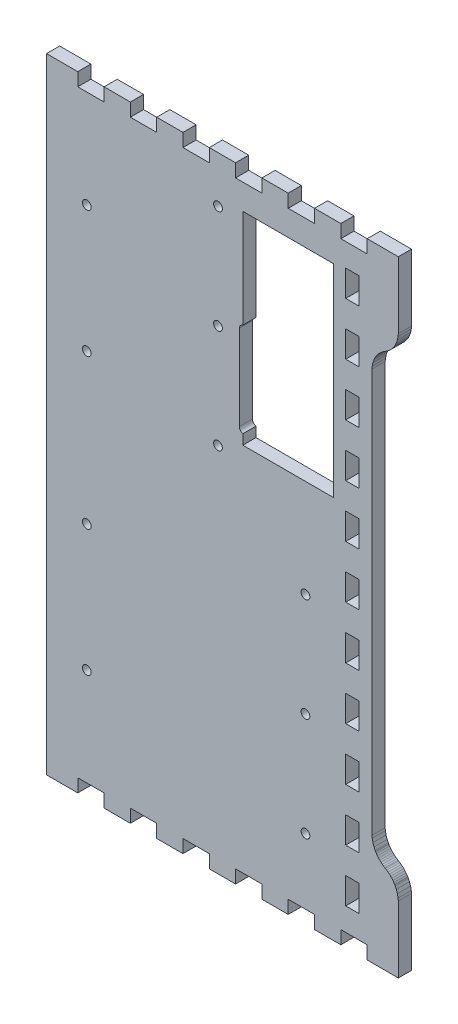
SolidWorks part; units mm, degrees
ref_plane "Front Plane" through (0, 0, 0) normal (0, 0, 1) x (1, 0, 0)
ref_plane "Top Plane" through (0, 0, 0) normal (0, 1, 0) x (1, 0, 0)
ref_plane "Right Plane" through (0, 0, 0) normal (1, 0, 0) x (0, 0, -1)
sketch "Model" plane through (0, 0, 0) normal (0, 0, 1) x (1, 0, 0)
  line L947 (1382.75, 22.8575) -> (1396.32, 22.8575)
  line L948 (1396.32, 22.8575) -> (1396.32, 28.5722)
  line L949 (1396.32, 28.5722) -> (1407.75, 28.5722)
  line L950 (1407.75, 28.5722) -> (1407.75, 22.8575)
  line L951 (1407.75, 22.8575) -> (1419.18, 22.8575)
  line L952 (1419.18, 22.8575) -> (1419.18, 28.5722)
  line L953 (1419.18, 28.5722) -> (1430.61, 28.5722)
  line L954 (1430.61, 28.5722) -> (1430.61, 22.8575)
  line L955 (1430.61, 22.8575) -> (1442.04, 22.8575)
  line L956 (1442.04, 22.8575) -> (1442.04, 28.5722)
  line L957 (1442.04, 28.5722) -> (1453.47, 28.5722)
  line L958 (1453.47, 28.5722) -> (1453.47, 22.8575)
  line L959 (1453.47, 22.8575) -> (1464.9, 22.8575)
  line L960 (1464.9, 22.8575) -> (1464.9, 28.5722)
  line L961 (1464.9, 28.5722) -> (1476.33, 28.5722)
  line L962 (1476.33, 28.5722) -> (1476.33, 22.8575)
  line L963 (1476.33, 22.8575) -> (1487.76, 22.8575)
  line L964 (1487.76, 22.8575) -> (1487.76, 28.5722)
  line L965 (1487.76, 28.5722) -> (1499.19, 28.5722)
  line L966 (1499.19, 28.5722) -> (1499.19, 22.8575)
  line L967 (1499.19, 22.8575) -> (1510.62, 22.8575)
  line L968 (1510.62, 22.8575) -> (1510.62, 28.5722)
  line L969 (1510.62, 28.5722) -> (1522.05, 28.5722)
  line L970 (1522.05, 28.5722) -> (1522.05, 22.8575)
  line L971 (1522.05, 22.8575) -> (1535.61, 22.8575)
  line L972 (1535.61, 22.8575) -> (1535.61, 28.5722)
  line L973 (1535.61, 28.5722) -> (1535.61, 51.4325)
  line L974 (1535.61, 51.4325) -> (1535.61, 51.8072)
  line L975 (1535.61, 51.8072) -> (1535.51, 52.9276)
  line L976 (1535.51, 52.9276) -> (1535.22, 54.3913)
  line L977 (1535.22, 54.3913) -> (1534.74, 55.8038)
  line L978 (1534.74, 55.8038) -> (1534.27, 56.8247)
  line L979 (1534.27, 56.8247) -> (1534.08, 57.1472)
  line L980 (1534.08, 57.1472) -> (1533.99, 57.3098)
  line L981 (1533.99, 57.3098) -> (1533.68, 57.7854)
  line L982 (1533.68, 57.7854) -> (1533.25, 58.3928)
  line L983 (1533.25, 58.3928) -> (1532.77, 58.9703)
  line L984 (1532.77, 58.9703) -> (1532.27, 59.5147)
  line L985 (1532.27, 59.5147) -> (1531.72, 60.0244)
  line L986 (1531.72, 60.0244) -> (1531.14, 60.4986)
  line L987 (1531.14, 60.4986) -> (1530.53, 60.9353)
  line L988 (1530.53, 60.9353) -> (1530.06, 61.2387)
  line L989 (1530.06, 61.2387) -> (1529.9, 61.3311)
  line L990 (1529.9, 61.3311) -> (1529.74, 61.4246)
  line L991 (1529.74, 61.4246) -> (1529.26, 61.728)
  line L992 (1529.26, 61.728) -> (1528.65, 62.1647)
  line L993 (1528.65, 62.1647) -> (1528.07, 62.6389)
  line L994 (1528.07, 62.6389) -> (1527.53, 63.1486)
  line L995 (1527.53, 63.1486) -> (1527.02, 63.693)
  line L996 (1527.02, 63.693) -> (1526.55, 64.2705)
  line L997 (1526.55, 64.2705) -> (1526.11, 64.878)
  line L998 (1526.11, 64.878) -> (1525.81, 65.3535)
  line L999 (1525.81, 65.3535) -> (1525.71, 65.5147)
  line L1000 (1525.71, 65.5147) -> (1525.53, 65.8386)
  line L1001 (1525.53, 65.8386) -> (1525.05, 66.8595)
  line L1002 (1525.05, 66.8595) -> (1524.57, 68.272)
  line L1003 (1524.57, 68.272) -> (1524.28, 69.7357)
  line L1004 (1524.28, 69.7357) -> (1524.18, 70.8561)
  line L1005 (1524.18, 70.8561) -> (1524.18, 71.2294)
  line L1006 (1524.18, 71.2294) -> (1524.18, 245.915)
  line L1007 (1524.18, 245.915) -> (1524.18, 246.29)
  line L1008 (1524.18, 246.29) -> (1524.28, 247.41)
  line L1009 (1524.28, 247.41) -> (1524.57, 248.874)
  line L1010 (1524.57, 248.874) -> (1525.05, 250.286)
  line L1011 (1525.05, 250.286) -> (1525.53, 251.307)
  line L1012 (1525.53, 251.307) -> (1525.71, 251.63)
  line L1013 (1525.71, 251.63) -> (1525.81, 251.792)
  line L1014 (1525.81, 251.792) -> (1526.11, 252.268)
  line L1015 (1526.11, 252.268) -> (1526.55, 252.876)
  line L1016 (1526.55, 252.876) -> (1527.02, 253.453)
  line L1017 (1527.02, 253.453) -> (1527.53, 253.997)
  line L1018 (1527.53, 253.997) -> (1528.07, 254.507)
  line L1019 (1528.07, 254.507) -> (1528.65, 254.981)
  line L1020 (1528.65, 254.981) -> (1529.26, 255.418)
  line L1021 (1529.26, 255.418) -> (1529.74, 255.72)
  line L1022 (1529.74, 255.72) -> (1529.9, 255.814)
  line L1023 (1529.9, 255.814) -> (1530.06, 255.907)
  line L1024 (1530.06, 255.907) -> (1530.53, 256.211)
  line L1025 (1530.53, 256.211) -> (1531.14, 256.647)
  line L1026 (1531.14, 256.647) -> (1531.72, 257.121)
  line L1027 (1531.72, 257.121) -> (1532.27, 257.631)
  line L1028 (1532.27, 257.631) -> (1532.77, 258.175)
  line L1029 (1532.77, 258.175) -> (1533.25, 258.753)
  line L1030 (1533.25, 258.753) -> (1533.68, 259.36)
  line L1031 (1533.68, 259.36) -> (1533.99, 259.836)
  line L1032 (1533.99, 259.836) -> (1534.08, 259.997)
  line L1033 (1534.08, 259.997) -> (1534.27, 260.321)
  line L1034 (1534.27, 260.321) -> (1534.74, 261.342)
  line L1035 (1534.74, 261.342) -> (1535.22, 262.755)
  line L1036 (1535.22, 262.755) -> (1535.51, 264.218)
  line L1037 (1535.51, 264.218) -> (1535.61, 265.339)
  line L1038 (1535.61, 265.339) -> (1535.61, 265.712)
  line L1039 (1535.61, 265.712) -> (1535.61, 288.572)
  line L1040 (1535.61, 288.572) -> (1535.61, 294.287)
  line L1041 (1535.61, 294.287) -> (1522.05, 294.287)
  line L1042 (1522.05, 294.287) -> (1522.05, 288.572)
  line L1043 (1522.05, 288.572) -> (1510.62, 288.572)
  line L1044 (1510.62, 288.572) -> (1510.62, 294.287)
  line L1045 (1510.62, 294.287) -> (1499.19, 294.287)
  line L1046 (1499.19, 294.287) -> (1499.19, 288.572)
  line L1047 (1499.19, 288.572) -> (1487.76, 288.572)
  line L1048 (1487.76, 288.572) -> (1487.76, 294.287)
  line L1049 (1487.76, 294.287) -> (1476.33, 294.287)
  line L1050 (1476.33, 294.287) -> (1476.33, 288.572)
  line L1051 (1476.33, 288.572) -> (1464.9, 288.572)
  line L1052 (1464.9, 288.572) -> (1464.9, 294.287)
  line L1053 (1464.9, 294.287) -> (1453.47, 294.287)
  line L1054 (1453.47, 294.287) -> (1453.47, 288.572)
  line L1055 (1453.47, 288.572) -> (1442.04, 288.572)
  line L1056 (1442.04, 288.572) -> (1442.04, 294.287)
  line L1057 (1442.04, 294.287) -> (1430.61, 294.287)
  line L1058 (1430.61, 294.287) -> (1430.61, 288.572)
  line L1059 (1430.61, 288.572) -> (1419.18, 288.572)
  line L1060 (1419.18, 288.572) -> (1419.18, 294.287)
  line L1061 (1419.18, 294.287) -> (1407.75, 294.287)
  line L1062 (1407.75, 294.287) -> (1407.75, 288.572)
  line L1063 (1407.75, 288.572) -> (1396.32, 288.572)
  line L1064 (1396.32, 288.572) -> (1396.32, 294.287)
  line L1065 (1396.32, 294.287) -> (1382.75, 294.287)
  line L1066 (1382.75, 294.287) -> (1382.75, 288.572)
  line L1067 (1382.75, 288.572) -> (1382.75, 28.5722)
  line L1068 (1382.75, 28.5722) -> (1382.75, 22.8575)
  line L1069 (1518.47, 44.2722) -> (1518.47, 38.5576)
  line L1070 (1518.47, 38.5576) -> (1512.75, 38.5576)
  line L1071 (1512.75, 38.5576) -> (1512.75, 49.9868)
  line L1072 (1512.75, 49.9868) -> (1518.47, 49.9868)
  line L1073 (1518.47, 49.9868) -> (1518.47, 44.2722)
  line L1074 (1518.47, 67.1326) -> (1518.47, 61.4179)
  line L1075 (1518.47, 61.4179) -> (1512.75, 61.4179)
  line L1076 (1512.75, 61.4179) -> (1512.75, 72.8472)
  line L1077 (1512.75, 72.8472) -> (1518.47, 72.8472)
  line L1078 (1518.47, 72.8472) -> (1518.47, 67.1326)
  line L1079 (1518.47, 89.9929) -> (1518.47, 84.2779)
  line L1080 (1518.47, 84.2779) -> (1512.75, 84.2779)
  line L1081 (1512.75, 84.2779) -> (1512.75, 95.7076)
  line L1082 (1512.75, 95.7076) -> (1518.47, 95.7076)
  line L1083 (1518.47, 95.7076) -> (1518.47, 89.9929)
  line L1084 (1518.47, 112.853) -> (1518.47, 107.137)
  line L1085 (1518.47, 107.137) -> (1512.75, 107.137)
  line L1086 (1512.75, 107.137) -> (1512.75, 118.568)
  line L1087 (1512.75, 118.568) -> (1518.47, 118.568)
  line L1088 (1518.47, 118.568) -> (1518.47, 112.853)
  line L1089 (1518.47, 135.712) -> (1518.47, 129.997)
  line L1090 (1518.47, 129.997) -> (1512.75, 129.997)
  line L1091 (1512.75, 129.997) -> (1512.75, 141.428)
  line L1092 (1512.75, 141.428) -> (1518.47, 141.428)
  line L1093 (1518.47, 141.428) -> (1518.47, 135.712)
  line L1094 (1518.47, 158.572) -> (1518.47, 152.858)
  line L1095 (1518.47, 152.858) -> (1512.75, 152.858)
  line L1096 (1512.75, 152.858) -> (1512.75, 164.287)
  line L1097 (1512.75, 164.287) -> (1518.47, 164.287)
  line L1098 (1518.47, 164.287) -> (1518.47, 158.572)
  line L1099 (1518.47, 181.433) -> (1518.47, 175.718)
  line L1100 (1518.47, 175.718) -> (1512.75, 175.718)
  line L1101 (1512.75, 175.718) -> (1512.75, 187.147)
  line L1102 (1512.75, 187.147) -> (1518.47, 187.147)
  line L1103 (1518.47, 187.147) -> (1518.47, 181.433)
  line L1104 (1518.47, 204.293) -> (1518.47, 198.578)
  line L1105 (1518.47, 198.578) -> (1512.75, 198.578)
  line L1106 (1512.75, 198.578) -> (1512.75, 210.008)
  line L1107 (1512.75, 210.008) -> (1518.47, 210.008)
  line L1108 (1518.47, 210.008) -> (1518.47, 204.293)
  line L1109 (1518.47, 227.153) -> (1518.47, 221.437)
  line L1110 (1518.47, 221.437) -> (1512.75, 221.437)
  line L1111 (1512.75, 221.437) -> (1512.75, 232.868)
  line L1112 (1512.75, 232.868) -> (1518.47, 232.868)
  line L1113 (1518.47, 232.868) -> (1518.47, 227.153)
  line L1114 (1518.47, 250.012) -> (1518.47, 244.297)
  line L1115 (1518.47, 244.297) -> (1512.75, 244.297)
  line L1116 (1512.75, 244.297) -> (1512.75, 255.728)
  line L1117 (1512.75, 255.728) -> (1518.47, 255.728)
  line L1118 (1518.47, 255.728) -> (1518.47, 250.012)
  line L1119 (1518.47, 272.872) -> (1518.47, 267.158)
  line L1120 (1518.47, 267.158) -> (1512.75, 267.158)
  line L1121 (1512.75, 267.158) -> (1512.75, 278.587)
  line L1122 (1512.75, 278.587) -> (1518.47, 278.587)
  line L1123 (1518.47, 278.587) -> (1518.47, 272.872)
extrude "Boss-Extrude1" add sketch "Model" along normal blind 5.715
sketch "Sketch1" plane through (0, 0, 0) normal (0, 0, -1) x (-1, 0, 0)
  line L20 (-1468.0398, 276.0723) -> (-1468.0398, 277.5723)
  line L21 (-1468.0398, 277.5723) -> (-1507.5398, 277.5723)
  line L22 (-1507.5398, 277.5723) -> (-1507.5398, 276.0723)
  line L23 (-1507.5398, 276.0723) -> (-1507.5398, 191.0723)
  line L24 (-1507.5398, 191.0723) -> (-1507.5398, 189.5723)
  line L25 (-1507.5398, 189.5723) -> (-1468.0398, 189.5723)
  line L26 (-1468.0398, 189.5723) -> (-1468.0398, 191.0723)
  line L27 (-1468.0398, 191.0723) -> (-1468.0398, 193.8858)
  line L28 (-1466.5398, 195.8223) -> (-1466.5398, 232.8223)
  line L29 (-1468.0398, 234.7588) -> (-1468.0398, 276.0723)
  line L30 (-1468.0398, 276.0723) -> (-1468.0398, 277.5723)
  line L31 (-1468.0398, 277.5723) -> (-1507.5398, 277.5723)
  line L32 (-1507.5398, 277.5723) -> (-1507.5398, 276.0723)
  line L33 (-1507.5398, 276.0723) -> (-1507.5398, 191.0723)
  line L34 (-1507.5398, 191.0723) -> (-1507.5398, 189.5723)
  line L35 (-1507.5398, 189.5723) -> (-1468.0398, 189.5723)
  line L36 (-1468.0398, 189.5723) -> (-1468.0398, 191.0723)
  line L37 (-1468.0398, 191.0723) -> (-1468.0398, 193.8858)
  line L38 (-1466.5398, 195.8223) -> (-1466.5398, 232.8223)
  line L39 (-1468.0398, 234.7588) -> (-1468.0398, 276.0723)
  arc A4 (-1468.0398, 193.8858) -> (-1466.5398, 195.8223) centre (-1468.5398, 195.8223) ccw
  arc A5 (-1466.5398, 232.8223) -> (-1468.0398, 234.7588) centre (-1468.5398, 232.8223) ccw
  arc A6 (-1468.0398, 193.8858) -> (-1466.5398, 195.8223) centre (-1468.5398, 195.8223) ccw
  arc A7 (-1466.5398, 232.8223) -> (-1468.0398, 234.7588) centre (-1468.5398, 232.8223) ccw
  dimension "D1" = 0.5
extrude "Cut-Extrude1" cut sketch "Sketch1" against normal through all
sketch "Sketch2" plane through (0, 0, 5.715) normal (0, 0, 1) x (1, 0, 0)
  point P0 (1400.25, 71.0721)
  point P1 (1400.25, 126.0721)
  point P3 (1400.25, 191.0721)
  point P5 (1400.25, 246.0721)
  point P7 (1457.2548, 184.072)
  point P9 (1457.2548, 229.072)
  point P11 (1457.2548, 274.072)
  point P13 (1495.2548, 57.0223)
  point P15 (1495.2548, 102.0223)
  point P17 (1495.2548, 147.0223)
hole_wizard "#6 Clearance Hole1" positions "Sketch5" profile "Sketch6" hole size "#6" standard "ANSI Inch" end condition through all
sketch "Sketch5" plane through (0, 0, 0) normal (0, 0, -1) x (-1, 0, 0)
  point P0 (-1400.25, 246.0721)
  point P3 (-1400.25, 191.0721)
  point P6 (-1400.25, 126.0721)
  point P9 (-1400.25, 71.0721)
  point P12 (-1457.2548, 274.072)
  point P15 (-1457.2548, 229.072)
  point P18 (-1457.2548, 184.072)
  point P21 (-1495.2548, 147.0223)
  point P24 (-1495.2548, 102.0223)
  point P27 (-1495.2548, 57.0223)
sketch "Sketch6" plane through (1400.25, 246.0721, 0) normal (1, 0, 0) x (0, 1, 0)
  line L0 (0, 0) -> (0, 5.715)
  line L1 (0, 5.715) -> (1.8986, 5.715)
  line L2 (1.8986, 5.715) -> (1.8986, 0)
  line L5 (1.8986, 0) -> (0, 0)
  line L11 (0, -6.35) -> (0, 107.95) construction
  dimension "Thru Hole Dia." = 3.7973
  dimension "Thru Hole Depth" = 5.715
